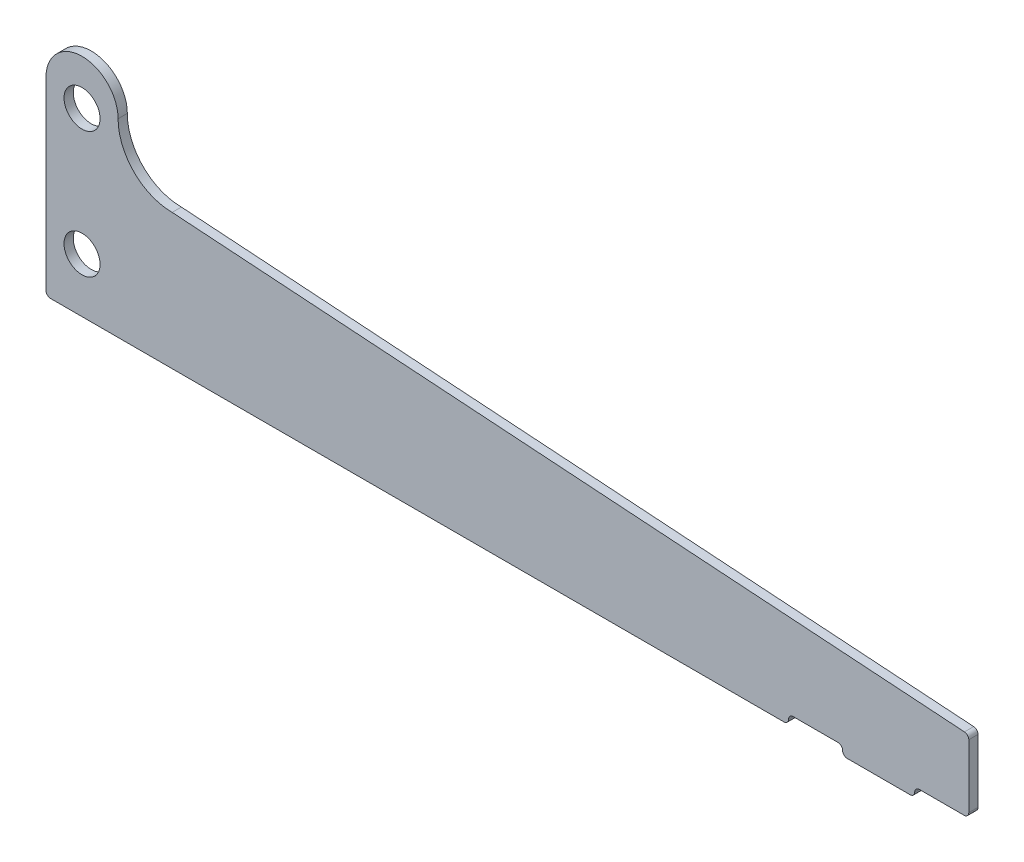
SolidWorks part; units mm, degrees
ref_plane "Front Plane" through (0, 0, 0) normal (0, 0, 1) x (1, 0, 0)
ref_plane "Top Plane" through (0, 0, 0) normal (0, 1, 0) x (1, 0, 0)
ref_plane "Right Plane" through (0, 0, 0) normal (1, 0, 0) x (0, 0, -1)
sketch "Sketch1" plane through (0, 0, 0) normal (0, 0, 1) x (1, 0, 0)
  line L0 (3.175, 19.05) -> (3.175, 0) construction
  line L1 (0, 0) -> (6.35, 0) construction
  line L2 (0, 0) -> (0, 19.05)
  line L3 (0, 19.05) -> (6.35, 19.05)
  line L4 (6.35, 0) -> (6.35, 19.05) construction
  line L5 (3.175, 15.0813) -> (3.175, 3.9688) construction
  line L6 (6.35, 0) -> (81.2824, 0) construction
  line L9 (0, 0) -> (0, -0.8128)
  line L10 (0, -0.8128) -> (81.2824, -0.8128)
  line L11 (81.2824, -0.8128) -> (81.2824, 0)
  line L12 (0, 19.05) -> (-1.5875, 19.05) construction
  line L13 (-1.5875, 19.05) -> (-1.5875, -0.8128) construction
  line L14 (-1.5875, -0.8128) -> (0, -0.8128) construction
  line L15 (81.2824, 11.1125) -> (6.35, 11.1125) construction
  line L16 (81.2824, 0) -> (81.2824, 11.1125) construction
  line L17 (11.1125, 11.1125) -> (81.2824, 6.35)
  line L18 (81.2824, 6.35) -> (81.2824, 0)
  line L21 (81.2824, -0.8128) -> (76.5199, -0.8128)
  line L22 (81.2824, -0.8128) -> (81.2824, 0)
  line L23 (81.2824, 0) -> (76.5199, 0)
  line L24 (76.5199, -0.8128) -> (76.5199, 0)
  line L25 (81.2824, -0.8128) -> (76.5199, 0) construction
  line L26 (81.2824, 0) -> (76.5199, -0.8128) construction
  line L27 (70.1699, 0) -> (65.4074, 0)
  line L28 (70.1699, 0) -> (70.1699, -0.8128)
  line L29 (70.1699, -0.8128) -> (65.4074, -0.8128)
  line L30 (65.4074, 0) -> (65.4074, -0.8128)
  line L31 (70.1699, 0) -> (65.4074, -0.8128) construction
  line L32 (70.1699, -0.8128) -> (65.4074, 0) construction
  circle A0 centre (3.175, 15.0813) radius 1.5875
  circle A1 centre (3.175, 3.9688) radius 1.5875
  circle A2 centre (3.175, 15.875) radius 3.175
  circle A3 centre (3.175, 3.175) radius 3.175
  circle A4 centre (11.1125, 15.875) radius 4.7625
  point P11 (3.175, 9.525)
  point P12 (3.175, 9.525)
  point P30 (6.35, 15.875)
  point P44 (78.9012, -0.4064)
  point P49 (67.7887, -0.4064)
  dimension "D1" = 19.05
  dimension "D2" = 3.175
  dimension "D8" = 11.1125
  dimension "D9" = 6.35
  dimension "D10" = 15.875
  dimension "D3" = 6.35
  dimension "D4" = 11.1125
  dimension "D5" = 0.8128
  dimension "D6" = 82.8699
  dimension "D7" = 1.5875
  dimension "D11" = 6.35
extrude "Boss-Extrude1" add sketch "Sketch1" along normal blind 0.8128 contours L17 A4 A2 L2 A3 L9 L10 L30 L27 L28 L24 | A3 A1 | A2 A0 | L24 L23 | L23 | L18 region at (3.175, 6.2602, 0) region at (37.2519, 4.5266, 0) region at (0.9934, 18.0566, 0)
fillet "Fillet1" radius 0.4064 9 edges at (81.2824, 6.35, 0.4064) (81.2824, 0, 0.4064) (76.5199, 0, 0.4064) (76.5199, -0.8128, 0.4064) (70.1699, -0.8128, 0.4064) (70.1699, 0, 0.4064) (65.4074, 0, 0.4064) (65.4074, -0.8128, 0.4064) (0, -0.8128, 0.4064)
